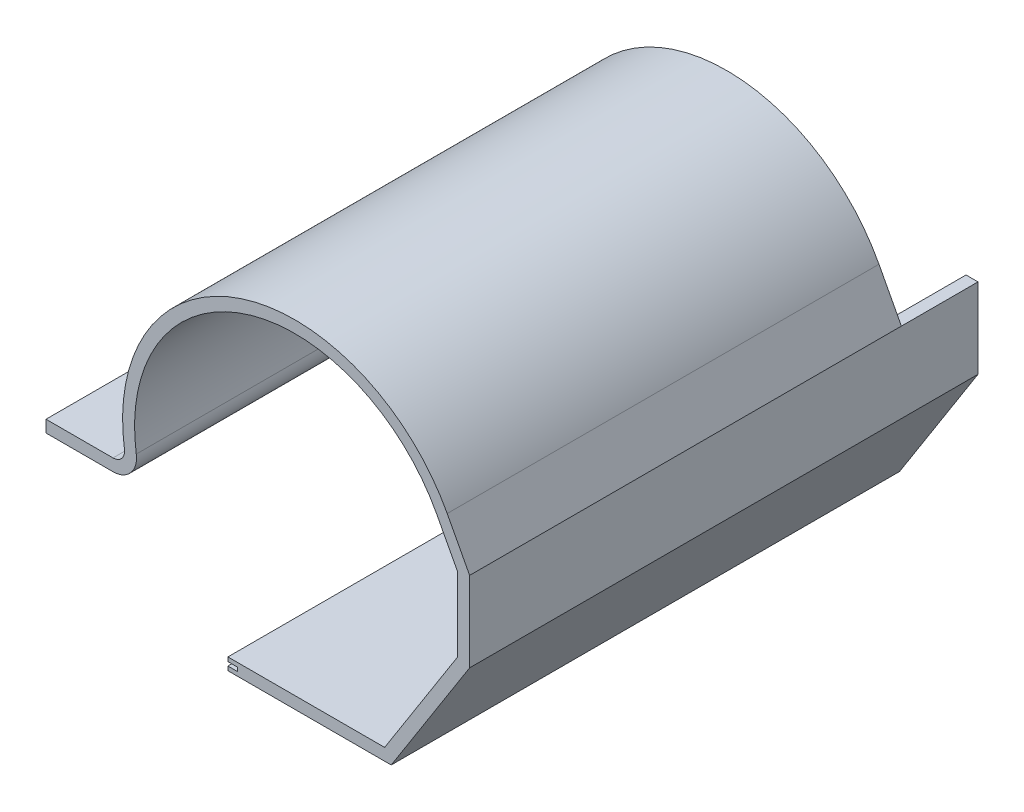
SolidWorks part; units mm, degrees
material "Thornel VCB-20 Carbon Cloth"
ref_plane "Front Plane" through (0, 0, 0) normal (0, 0, 1) x (1, 0, 0)
ref_plane "Top Plane" through (0, 0, 0) normal (0, 1, 0) x (1, 0, 0)
ref_plane "Right Plane" through (0, 0, 0) normal (1, 0, 0) x (0, 0, -1)
sketch "Sketch3" plane through (0, 0, 0) normal (0, 0, 1) x (1, 0, 0)
  line L0 (-7.5, -25) -> (7.5, -25) construction
  line L3 (-20, -10) -> (20, -10)
  line L4 (-20, -40) -> (-20, -10)
  line L5 (-20, -40) -> (20, -40)
  line L6 (20, -40) -> (20, -10)
  line L7 (0, -40) -> (0, -10) construction
  line L8 (0, -10) -> (0, 0) construction
  circle A2 centre (7.5, -25) radius 2.5
  circle A3 centre (-7.5, -25) radius 2.5
  point P11 (0, -25)
  dimension "D4" = 5
  dimension "D5" = 5
  dimension "D1" = 15
  dimension "D2" = 40
  dimension "D3" = 30
  dimension "D6" = 15
  dimension "D7" = 10
extrude "Boss-Extrude2" add sketch "Sketch3" along normal blind 6.25
sketch "Sketch4" plane through (0, 0, 6.25) normal (0, 0, 1) x (1, 0, 0)
  line L0 (20, -40) -> (20, -10) construction
  line L1 (-20, -40) -> (20, -40)
  line L2 (-20, -40) -> (-20, -33.75)
  line L3 (-20, -33.75) -> (20, -33.75)
  line L4 (20, -40) -> (20, -33.75)
  dimension "D1" = 6.25
extrude "Boss-Extrude3" add sketch "Sketch4" along normal blind 7.5
sketch "Sketch5" plane through (0, 0, 13.75) normal (0, 0, 1) x (1, 0, 0)
  line L1 (-20, -40) -> (-88.4287, -40)
  line L12 (-110.625, -10.9092) -> (-90.1451, -43.125)
  line L13 (0, -33.75) -> (0, -40) construction
  line L27 (-107.5, -10) -> (-88.4287, -40)
  line L29 (-107.5, 10) -> (-107.5, -10)
  line L30 (-107.5, 10) -> (-110.625, 10)
  line L31 (-110.625, 10) -> (-110.625, -10.9092)
  line L32 (110.625, 10) -> (110.625, -10.9092)
  line L33 (107.5, 10) -> (110.625, 10)
  line L34 (107.5, 10) -> (107.5, -10)
  line L35 (107.5, -10) -> (88.4287, -40)
  line L36 (110.625, -10.9092) -> (90.1451, -43.125)
  line L38 (20, -40) -> (88.4287, -40)
  line L39 (-90.1451, -43.125) -> (90.1451, -43.125)
  line L40 (-20, -40) -> (20, -40) construction
  line L41 (-20, -40) -> (20, -40)
  arc A1 (-104.9218, -10.3078) -> (-55, -40) centre (-65, 0) ccw construction
  arc A4 (104.9218, -10.3078) -> (55, -40) centre (65, 0) cw construction
  dimension "D3" = 3.125
  dimension "D2" = 3.125
  dimension "D4" = 3.125
  dimension "D7" = 20
  dimension "D1" = 10
  dimension "D5" = 42.5
  dimension "D6" = 50
  dimension "D8" = 65
extrude "Boss-Extrude4" add sketch "Sketch5" against normal blind 20
chamfer "Chamfer1" distance 2.5 angle 45 4 edges at (-20, -10, 3.125) (20, -10, 3.125) (-20, -40, 6.875) (20, -40, 6.875)
sketch "Sketch6" plane through (0, 0, 13.75) normal (0, 0, 1) x (1, 0, 0)
  line L0 (-110.625, 10) -> (-104.7676, 21.0604)
  line L1 (-90.1451, -43.125) -> (90.1451, -43.125) construction
  line L2 (-110.625, -10.9092) -> (-90.1451, -43.125) construction
  line L3 (-110.625, 10) -> (-110.625, -10.9092) construction
  line L4 (-90.1451, -43.125) -> (90.1451, -43.125)
  line L5 (-110.625, -10.9092) -> (-90.1451, -43.125)
  line L6 (-110.625, 10) -> (-110.625, -10.9092)
  line L7 (0, 0) -> (0, -43.125) construction
  line L9 (-65, 0) -> (0, 0) construction
  line L11 (17.5, -10) -> (-17.5, -10)
  line L15 (110.625, 10) -> (110.625, -10.9092)
  line L16 (110.625, -10.9092) -> (90.1451, -43.125)
  line L17 (110.625, 10) -> (104.7676, 21.0604)
  circle A1 centre (-65, 0) radius 38
  arc A3 (-20.4793, -6.5503) -> (-104.7676, 21.0604) centre (-65, 0) ccw
  arc A5 (-20.4793, -6.5503) -> (-17.5, -10) centre (-17.5, -6.9886) ccw
  arc A6 (20.4793, -6.5503) -> (17.5, -10) centre (17.5, -6.9886) cw
  arc A7 (20.4793, -6.5503) -> (104.7676, 21.0604) centre (65, 0) cw
  circle A8 centre (65, 0) radius 38
  point P26 (0, -10)
  dimension "D1" = 76
  dimension "D2" = 65
  dimension "D3" = 45
extrude "Boss-Extrude5" add sketch "Sketch6" along normal blind 12.25
sketch "Sketch8" plane through (0, 0, 26) normal (0, 0, 1) x (1, 0, 0)
  line L0 (-65, 0) -> (0, 0) construction
  line L1 (0, 0) -> (0, -43.125) construction
  line L2 (-90.1451, -43.125) -> (90.1451, -43.125) construction
  line L13 (-104.7676, 21.0604) -> (-110.625, 10)
  line L14 (-110.625, 10) -> (-110.625, -10.9092)
  line L15 (-110.625, -10.9092) -> (-90.1451, -43.125)
  line L16 (-90.1451, -43.125) -> (90.1451, -43.125)
  line L17 (90.1451, -43.125) -> (110.625, -10.9092)
  line L18 (110.625, -10.9092) -> (110.625, 10)
  line L19 (110.625, 10) -> (104.7676, 21.0604)
  line L21 (17.5, -10) -> (-17.5, -10)
  line L23 (-104.7676, 21.0604) -> (-110.625, 10)
  line L24 (-110.625, 10) -> (-110.625, -10.9092)
  line L25 (-110.625, -10.9092) -> (-90.1451, -43.125)
  line L26 (-90.1451, -43.125) -> (90.1451, -43.125)
  line L27 (90.1451, -43.125) -> (110.625, -10.9092)
  line L28 (110.625, -10.9092) -> (110.625, 10)
  line L29 (110.625, 10) -> (104.7676, 21.0604)
  line L31 (17.5, -10) -> (-17.5, -10)
  circle A0 centre (-65, 0) radius 28
  circle A1 centre (65, 0) radius 28
  arc A5 (-20.4793, -6.5503) -> (-104.7676, 21.0604) centre (-65, 0) ccw
  arc A6 (104.7676, 21.0604) -> (20.4793, -6.5503) centre (65, 0) ccw
  arc A7 (17.5, -10) -> (20.4793, -6.5503) centre (17.5, -6.9886) ccw
  arc A8 (-20.4793, -6.5503) -> (-17.5, -10) centre (-17.5, -6.9886) ccw
  arc A9 (-20.4793, -6.5503) -> (-104.7676, 21.0604) centre (-65, 0) ccw
  arc A10 (104.7676, 21.0604) -> (20.4793, -6.5503) centre (65, 0) ccw
  arc A11 (17.5, -10) -> (20.4793, -6.5503) centre (17.5, -6.9886) ccw
  arc A12 (-20.4793, -6.5503) -> (-17.5, -10) centre (-17.5, -6.9886) ccw
  dimension "D1" = 56
  dimension "D2" = 0
extrude "Boss-Extrude7" add sketch "Sketch8" along normal blind 10.5
sketch "Sketch9" plane through (0, 0, 36.5) normal (0, 0, 1) x (1, 0, 0)
  line L0 (0, 0) -> (0, -43.125) construction
  line L1 (-90.1451, -43.125) -> (90.1451, -43.125) construction
  circle A2 centre (65, 0) radius 31.125
  circle A3 centre (-65, 0) radius 31.125
  circle A4 centre (-65, 0) radius 31.125
  dimension "D1" = 3.125
extrude "Boss-Extrude8" add sketch "Sketch9" along normal blind 3.125
fillet "Fillet1" radius 4 2 edges at (33.875, 0, 36.5) (-33.875, 0, 36.5)
sketch "Sketch10" plane through (0, 0, 36.5) normal (0, 0, 1) x (1, 0, 0)
  line L10 (-104.7676, 21.0604) -> (-110.625, 10)
  line L11 (-110.625, 10) -> (-110.625, -10.9092)
  line L12 (-110.625, -10.9092) -> (-90.1451, -43.125)
  line L13 (-90.1451, -43.125) -> (90.1451, -43.125)
  line L14 (90.1451, -43.125) -> (110.625, -10.9092)
  line L15 (110.625, -10.9092) -> (110.625, 10)
  line L16 (110.625, 10) -> (104.7676, 21.0604)
  line L18 (17.5, -10) -> (-17.5, -10)
  line L20 (-104.7676, 21.0604) -> (-110.625, 10)
  line L21 (-110.625, 10) -> (-110.625, -10.9092)
  line L22 (-110.625, -10.9092) -> (-90.1451, -43.125)
  line L23 (-90.1451, -43.125) -> (-47.5, -43.125)
  line L24 (90.1451, -43.125) -> (110.625, -10.9092)
  line L25 (110.625, -10.9092) -> (110.625, 10)
  line L26 (110.625, 10) -> (104.7676, 21.0604)
  line L28 (17.5, -10) -> (-17.5, -10)
  line L30 (-47.5, -43.125) -> (-47.5, -40)
  line L31 (47.5, -43.125) -> (47.5, -40)
  line L32 (47.5, -43.125) -> (90.1451, -43.125)
  line L33 (47.5, -40) -> (88.4287, -40)
  line L40 (-102.006, 19.5978) -> (-107.5, 9.2236)
  line L41 (-107.5, 9.2236) -> (-107.5, -10)
  line L42 (-107.5, -10) -> (-88.4287, -40)
  line L43 (-88.4287, -40) -> (88.4287, -40)
  line L44 (88.4287, -40) -> (107.5, -10)
  line L45 (107.5, -10) -> (107.5, 9.2236)
  line L46 (107.5, 9.2236) -> (102.006, 19.5978)
  line L48 (17.5, -13.125) -> (-17.5, -13.125)
  line L50 (-102.006, 19.5978) -> (-107.5, 9.2236)
  line L51 (-107.5, 9.2236) -> (-107.5, -10)
  line L52 (-107.5, -10) -> (-88.4287, -40)
  line L53 (-88.4287, -40) -> (-47.5, -40)
  line L54 (88.4287, -40) -> (107.5, -10)
  line L55 (107.5, -10) -> (107.5, 9.2236)
  line L56 (107.5, 9.2236) -> (102.006, 19.5978)
  line L58 (17.5, -13.125) -> (-17.5, -13.125)
  arc A4 (-20.4793, -6.5503) -> (-104.7676, 21.0604) centre (-65, 0) ccw
  arc A5 (104.7676, 21.0604) -> (20.4793, -6.5503) centre (65, 0) ccw
  arc A6 (17.5, -10) -> (20.4793, -6.5503) centre (17.5, -6.9886) ccw
  arc A7 (-20.4793, -6.5503) -> (-17.5, -10) centre (-17.5, -6.9886) ccw
  arc A8 (-20.4793, -6.5503) -> (-104.7676, 21.0604) centre (-65, 0) ccw
  arc A9 (104.7676, 21.0604) -> (20.4793, -6.5503) centre (65, 0) ccw
  arc A10 (17.5, -10) -> (20.4793, -6.5503) centre (17.5, -6.9886) ccw
  arc A11 (-20.4793, -6.5503) -> (-17.5, -10) centre (-17.5, -6.9886) ccw
  arc A16 (-23.571, -6.0954) -> (-102.006, 19.5978) centre (-65, 0) ccw
  arc A17 (102.006, 19.5978) -> (23.571, -6.0954) centre (65, 0) ccw
  arc A18 (17.5, -13.125) -> (23.571, -6.0954) centre (17.5, -6.9886) ccw
  arc A19 (-23.571, -6.0954) -> (-17.5, -13.125) centre (-17.5, -6.9886) ccw
  arc A20 (-23.571, -6.0954) -> (-102.006, 19.5978) centre (-65, 0) ccw
  arc A21 (102.006, 19.5978) -> (23.571, -6.0954) centre (65, 0) ccw
  arc A22 (17.5, -13.125) -> (23.571, -6.0954) centre (17.5, -6.9886) ccw
  arc A23 (-23.571, -6.0954) -> (-17.5, -13.125) centre (-17.5, -6.9886) ccw
  dimension "D3" = 47.5
  dimension "D4" = 47.5
  dimension "D1" = 0
  dimension "D2" = 3.125
extrude "Boss-Extrude9" add sketch "Sketch10" along normal blind 90
mirror "Mirror1" about plane through (-65, 0, 126.5) normal (0, 0, 1) of "Boss-Extrude2", "Boss-Extrude3", "Boss-Extrude4", "Chamfer1", "Boss-Extrude5", "Boss-Extrude7", "Boss-Extrude8", "Fillet1", "Boss-Extrude9"
ref_plane "Plane1" through (0, 0, 126.5) normal (0, 0, -1) x (-1, 0, 0)
sketch "Sketch12" plane through (0, 0, 253) normal (0, 0, 1) x (1, 0, 0)
  line L8 (-20, -12.5) -> (-20, -37.5)
  line L9 (-20, -37.5) -> (-22.5, -40)
  line L10 (-22.5, -40) -> (22.5, -40)
  line L11 (22.5, -40) -> (20, -37.5)
  line L12 (20, -37.5) -> (20, -12.5)
  line L13 (20, -12.5) -> (17.5, -10)
  line L14 (17.5, -10) -> (-17.5, -10)
  line L15 (-17.5, -10) -> (-20, -12.5)
  line L16 (-20, -12.5) -> (-20, -37.5)
  line L17 (-20, -37.5) -> (-22.5, -40)
  line L18 (-22.5, -40) -> (22.5, -40)
  line L19 (22.5, -40) -> (20, -37.5)
  line L20 (20, -37.5) -> (20, -12.5)
  line L21 (20, -12.5) -> (17.5, -10)
  line L22 (17.5, -10) -> (-17.5, -10)
  line L23 (-17.5, -10) -> (-20, -12.5)
  circle A0 centre (7.5, -25) radius 2.5 construction
  circle A1 centre (-7.5, -25) radius 2.5 construction
  circle A2 centre (7.5, -25) radius 2.5
  circle A3 centre (-7.5, -25) radius 2.5
  dimension "D1" = 0
extrude "Boss-Extrude10" add sketch "Sketch12" against normal blind 30
mirror "Mirror2" about plane through (0, 0, 126.5) normal (0, 0, -1) of "Boss-Extrude10"
sketch "Sketch13" plane through (0, 0, 0) normal (1, 0, 0) x (0, 0, -1)
  line L0 (-216.5, -43.125) -> (-41.5, -43.125)
  line L1 (-36.5, -38.125) -> (-36.5, -25.2895)
  line L2 (-36.5, 35.0281) -> (-36.5, -35.0281) construction
  line L3 (-41.5, -20.2895) -> (-126.5, -20.2895)
  arc A0 (-36.5, -25.2895) -> (-41.5, -20.2895) centre (-41.5, -25.2895) ccw
  arc A1 (-41.5, -43.125) -> (-36.5, -38.125) centre (-41.5, -38.125) ccw
  point P10 (-36.5, -20.2895)
  point P13 (-36.5, -43.125)
  dimension "D1" = 5
sketch "Sketch14" plane through (0, -43.125, 0) normal (0, -1, 0) x (1, 0, 0)
  line L0 (0, 259.25) -> (0, 237.75) construction
  line L1 (-90.1451, 259.25) -> (90.1451, 259.25) construction
  line L2 (-10, 237.75) -> (10, 237.75) construction
  line L3 (-47.5, 126.5) -> (47.5, 126.5) construction
  line L4 (-47.5, 216.5) -> (-47.5, 36.5) construction
  line L5 (47.5, 216.5) -> (47.5, 36.5) construction
  line L6 (-10, 15.25) -> (10, 15.25) construction
  line L7 (0, -6.25) -> (0, 15.25) construction
  circle A0 centre (10, 237.75) radius 2.5
  circle A1 centre (-10, 237.75) radius 2.5
  circle A2 centre (-10, 15.25) radius 2.5
  circle A3 centre (10, 15.25) radius 2.5
  dimension "D3" = 5
  dimension "D1" = 21.5
  dimension "D2" = 10
extrude "Cut-Extrude1" cut sketch "Sketch14" against normal blind 10
sketch "Sketch16" plane through (0, 0, 0) normal (1, 0, 0) x (0, 0, -1)
  line L0 (-216.5, -41.5625) -> (-36.5, -41.5625) construction
  line L1 (-216.5, -43.125) -> (-216.5, -40) construction
  line L2 (-36.5, -43.125) -> (-36.5, -40) construction
  line L3 (-215.5, -41.0625) -> (-215.5, -40)
  line L4 (-36.5, -42.0625) -> (-216.5, -42.0625)
  line L5 (-36.5, -42.0625) -> (-36.5, -41.0625)
  line L6 (-36.5, -41.0625) -> (-215.5, -41.0625)
  line L7 (-216.5, -42.0625) -> (-216.5, -41.0625)
  line L8 (-36.5, -42.0625) -> (-126.5, -41.5625) construction
  line L9 (-36.5, -41.0625) -> (-216.5, -42.0625) construction
  line L10 (-216.5, -40) -> (-36.5, -40) construction
  line L11 (-215.5, -40) -> (-216.5, -40)
  line L12 (-216.5, -40) -> (-216.5, -10) construction
  line L13 (-216.5, -40) -> (-216.5, -41.0625)
  point P6 (-126.5, -41.5625)
  dimension "D1" = 1
  dimension "D2" = 1
extrude "Cut-Extrude2" cut sketch "Sketch16" along normal mid plane 100
sketch "Sketch17" plane through (-47.5, 0, 0) normal (1, 0, 0) x (0, 0, -1)
  line L0 (-214.5, -41.0625) -> (-214.5, -34.8273)
  line L1 (-36.5, -41.0625) -> (-215.5, -41.0625) construction
  line L2 (-214.5, -34.8273) -> (-215.5, -34.8273)
  line L3 (-215.5, -34.8273) -> (-215.5, -41.0625)
  line L4 (-216.5, -40) -> (-216.5, -10) construction
  line L5 (-215.5, -41.0625) -> (-214.5, -41.0625)
  dimension "D1" = 1
  dimension "D2" = 1
extrude "Boss-Extrude11" add sketch "Sketch17" against normal blind 5
fillet "Fillet2" radius 0.5 2 edges at (-48.75, -41.0625, 215.5) (-50, -40, 214.5)
mirror "Mirror3" about plane through (0, 0, 0) normal (1, 0, 0) of "Cut-Extrude2", "Boss-Extrude11"
fillet "Fillet3" radius 0.5 2 edges at (48.75, -41.0625, 215.5) (50, -40, 214.5)
sketch "Sketch18" plane through (0, 0, 126.5) normal (0, 0, -1) x (-1, 0, 0)
  line L1 (-262.1903, 47.4799) -> (262.1903, 47.4799)
  line L2 (-262.1903, 47.4799) -> (-262.1903, -47.4799)
  line L3 (-262.1903, -47.4799) -> (262.1903, -47.4799)
  line L4 (262.1903, 47.4799) -> (262.1903, -47.4799)
  line L5 (-262.1903, 47.4799) -> (262.1903, -47.4799) construction
  line L6 (-262.1903, -47.4799) -> (262.1903, 47.4799) construction
  point P0 (0, 0)
extrude "Cut-Extrude3" cut sketch "Sketch18" against normal blind 174
sketch "Sketch19" plane through (0, 0, 0) normal (1, 0, 0) x (0, 0, -1)
  line L0 (-126.5, 10) -> (-13.75, 10) construction
  line L1 (82.0127, -79.6128) -> (-190.937, -79.6128)
  line L2 (82.0127, -79.6128) -> (82.0127, 99.6128)
  line L3 (82.0127, 99.6128) -> (-190.937, 99.6128)
  line L4 (-190.937, -79.6128) -> (-190.937, 99.6128)
  line L5 (82.0127, -79.6128) -> (-190.937, 99.6128) construction
  line L6 (82.0127, 99.6128) -> (-190.937, -79.6128) construction
  point P0 (-54.4621, 10)
extrude "Cut-Extrude4" cut sketch "Sketch19" against normal blind 174
equation "\"a\"=3.125"
equation "\"D3@Sketch5\"=\"a\""
equation "\"D2@Sketch5\"=\"a\""
equation "\"D4@Sketch5\"=\"a\""
